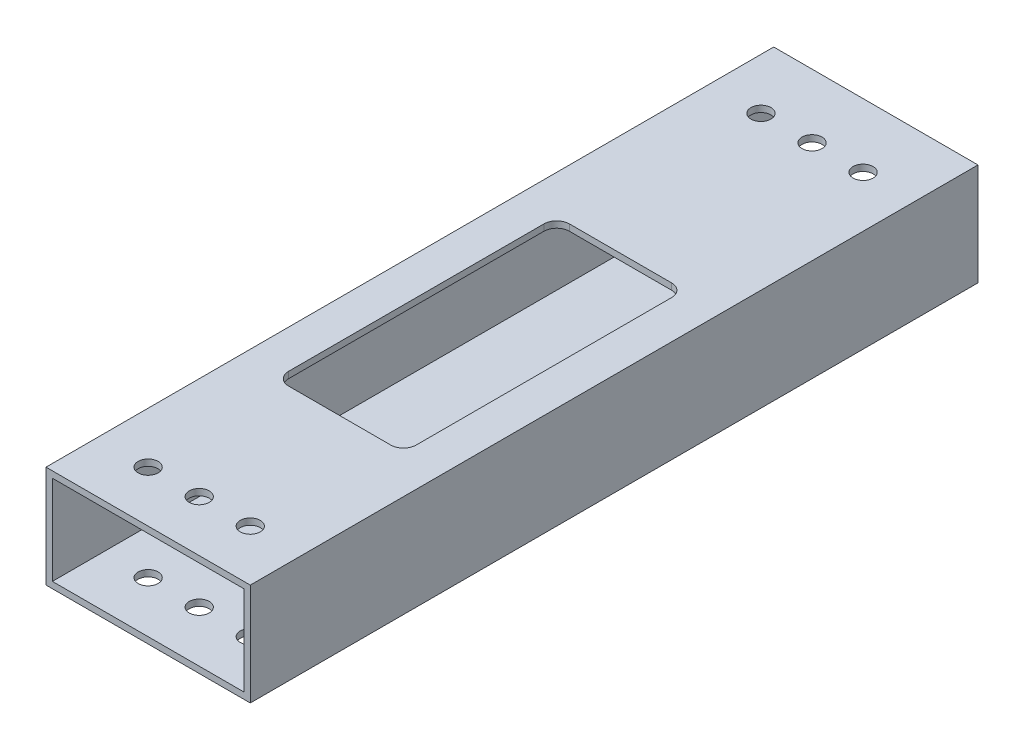
SolidWorks part; units mm, degrees
other "Markup4"
sketch "Sketch7" plane through (25.4, -12.7, 0) normal (0.9921, -0.1226, -0.0275) x (-0.1217, -0.992, 0.0335)
other "Markup5"
sketch "Sketch10"
material "6061-T6 (SS)"
ref_plane "Front Plane" through (0, 0, 0) normal (0, 0, 1) x (1, 0, 0)
ref_plane "Top Plane" through (0, 0, 0) normal (0, 1, 0) x (1, 0, 0)
ref_plane "Right Plane" through (0, 0, 0) normal (1, 0, 0) x (0, 0, -1)
sketch "Sketch1" plane through (0, 0, 0) normal (0, 0, 1) x (1, 0, 0)
  line L1 (-25.4, -12.7) -> (25.4, -12.7)
  line L2 (-25.4, -12.7) -> (-25.4, 12.7)
  line L3 (-25.4, 12.7) -> (25.4, 12.7)
  line L4 (25.4, -12.7) -> (25.4, 12.7)
  line L5 (-25.4, -12.7) -> (25.4, 12.7) construction
  line L6 (-25.4, 12.7) -> (25.4, -12.7) construction
  line L7 (-23.8125, -11.1125) -> (23.8125, -11.1125)
  line L8 (-23.8125, -11.1125) -> (-23.8125, 11.1125)
  line L9 (-23.8125, 11.1125) -> (23.8125, 11.1125)
  line L10 (23.8125, -11.1125) -> (23.8125, 11.1125)
  line L11 (-23.8125, -11.1125) -> (23.8125, 11.1125) construction
  line L12 (-23.8125, 11.1125) -> (23.8125, -11.1125) construction
  point P0 (0, 0)
  point P6 (0, 0)
  dimension "D1" = 50.8
  dimension "D2" = 25.4
  dimension "D3" = 1.5875
  dimension "D4" = 1.5875
extrude "Boss-Extrude1" add sketch "Sketch1" along normal blind 180.975
sketch "Sketch2" plane through (0, 12.7, 0) normal (0, 1, 0) x (1, 0, 0)
  line L0 (25.4, 0) -> (-25.4, 0) construction
  line L3 (25.4, -180.975) -> (-25.4, -180.975) construction
  circle A0 centre (-12.7, -15.875) radius 2.4892
  circle A1 centre (0, -15.875) radius 2.4892
  circle A2 centre (12.7, -15.875) radius 2.4892
  circle A3 centre (-12.7, -168.275) radius 2.4892
  circle A4 centre (0, -168.275) radius 2.4892
  circle A5 centre (12.7, -168.275) radius 2.4892
  dimension "D1" = 4.9784
  dimension "D2" = 15.875
  dimension "D3" = 12.7
  dimension "D4" = 12.7
  dimension "D5" = 12.7
extrude "Cut-Extrude1" cut sketch "Sketch2" against normal through all
sketch "Sketch9" plane through (0, 12.7, 0) normal (0, 1, 0) x (1, 0, 0)
  line L0 (25.4, 0) -> (-25.4, 0) construction
  line L1 (-15.875, -63.5) -> (15.875, -63.5)
  line L2 (-15.875, -63.5) -> (-15.875, -133.35)
  line L3 (-15.875, -133.35) -> (15.875, -133.35)
  line L4 (15.875, -63.5) -> (15.875, -133.35)
  line L5 (-25.4, -180.975) -> (-25.4, 0) construction
  point P8 (12.7, -95.0546)
  point P9 (-15.875, -81.8202)
  dimension "D1" = 63.5
  dimension "D2" = 31.75
  dimension "D3" = 9.525
  dimension "D4" = 69.85
extrude "Cut-Extrude2" cut sketch "Sketch9" against normal up to surface (23.8125 mm away) up to face at (0, -11.1125, 18.3642)
fillet "Fillet1" radius 3.175 4 edges at (-15.875, 11.9062, 63.5) (15.875, 11.9062, 133.35) (-15.875, 11.9062, 133.35) (15.875, 11.9062, 63.5)
